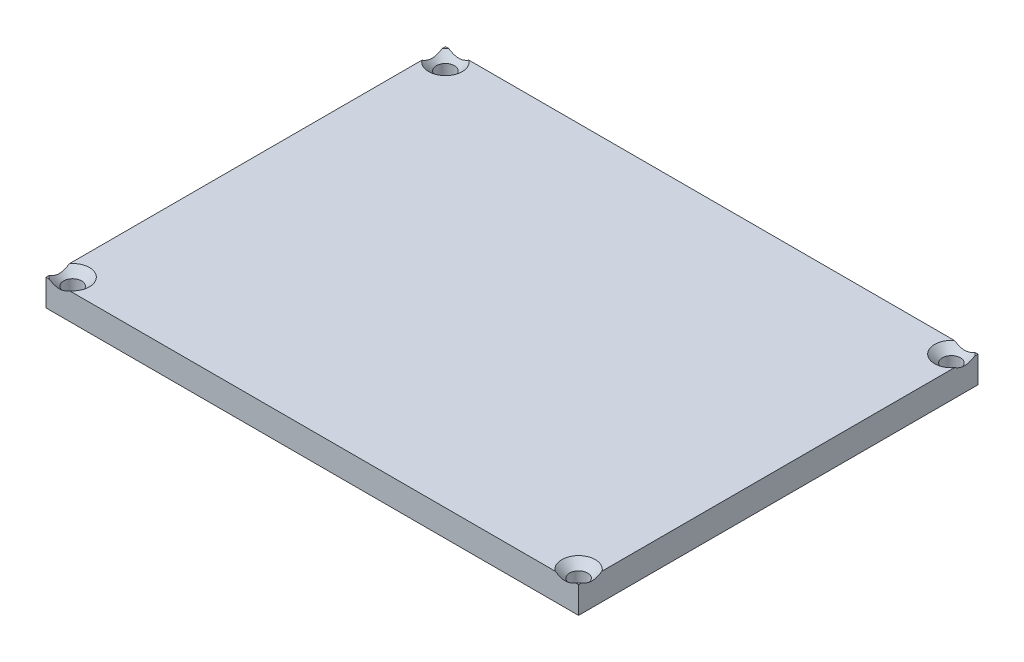
SolidWorks part; units mm, degrees
ref_plane "Alzado" through (0, 0, 0) normal (0, 0, 1) x (1, 0, 0)
ref_plane "Planta" through (0, 0, 0) normal (0, 1, 0) x (1, 0, 0)
ref_plane "Vista lateral" through (0, 0, 0) normal (1, 0, 0) x (0, 0, -1)
sketch "Croquis1" plane through (0, 0, 0) normal (0, 1, 0) x (1, 0, 0)
  line L1 (-67.5839, 18.7136) -> (32.4161, 18.7136)
  line L2 (-67.5839, 18.7136) -> (-67.5839, -56.2864)
  line L3 (-67.5839, -56.2864) -> (32.4161, -56.2864)
  line L4 (32.4161, 18.7136) -> (32.4161, -56.2864)
  dimension "D1" = 100
  dimension "D2" = 75
extrude "Saliente-Extruir1" add sketch "Croquis1" along normal blind 5
sketch "Croquis2" plane through (0, 0, 0) normal (0, 1, 0) x (1, 0, 0)
  line L0 (-67.5839, 18.7136) -> (-67.5839, -56.2864) construction
  line L1 (32.4161, 18.7136) -> (-67.5839, 18.7136) construction
  line L2 (32.4161, -56.2864) -> (32.4161, 18.7136) construction
  line L3 (-67.5839, -56.2864) -> (32.4161, -56.2864) construction
  point P0 (-65.0839, 16.2136)
  point P1 (29.9161, 16.2136)
  point P2 (29.9161, -53.7864)
  point P3 (-65.0839, -53.7864)
  dimension "D1" = 2.5
  dimension "D2" = 2.5
  dimension "D3" = 2.5
  dimension "D4" = 2.5
  dimension "D5" = 2.5
  dimension "D6" = 2.5
  dimension "D7" = 2.5
  dimension "D8" = 2.5
hole_wizard "Avellanado para tornillo con cabeza plana avellanada de M31" positions "Croquis3D1" profile "Croquis3" countersink size "M3" standard "DIN" end condition through all
sketch3d "Croquis3D1"
  line L0 (-67.5839, 5, -18.7136) -> (-67.5839, 5, 56.2864) construction
  line L1 (-67.5839, 5, 56.2864) -> (32.4161, 5, 56.2864) construction
  point P0 (-65.0839, 0, -16.2136)
  point P3 (29.9161, 0, -16.2136)
  point P6 (29.9161, 0, 53.7864)
  point P9 (-65.0839, 0, 53.7864)
  point P12 (-65.0839, 5, -16.2136)
  point P15 (29.9161, 5, -16.2136)
  point P17 (29.9161, 5, 53.7864)
  point P19 (-65.0839, 5, 53.7864)
  dimension "D1" = 2.5
  dimension "D2" = 2.5
  dimension "D3" = 2.5
  dimension "D4" = 2.5
sketch "Croquis3" plane through (-65.0839, 5, 53.7864) normal (1, 0, 0) x (0, 0, 1)
  line L0 (0, 0) -> (0, 5)
  line L1 (0, 5) -> (1.7, 5)
  line L2 (1.7, 5) -> (1.7, 1.45)
  line L3 (1.7, 1.45) -> (3.15, 0)
  line L5 (3.15, 0) -> (0, 0)
  line L6 (-1.7, 1.45) -> (-3.15, 0) construction
  line L11 (0, -6.35) -> (0, 107.95) construction
  dimension "Diámetro de taladro hasta el siguiente" = 3.4
  dimension "Profundidad de taladro hasta el siguiente" = 5
  dimension "Diámetro de avellanado cercano" = 6.3
  dimension "Ángulo de avellanado cercano" = 90
